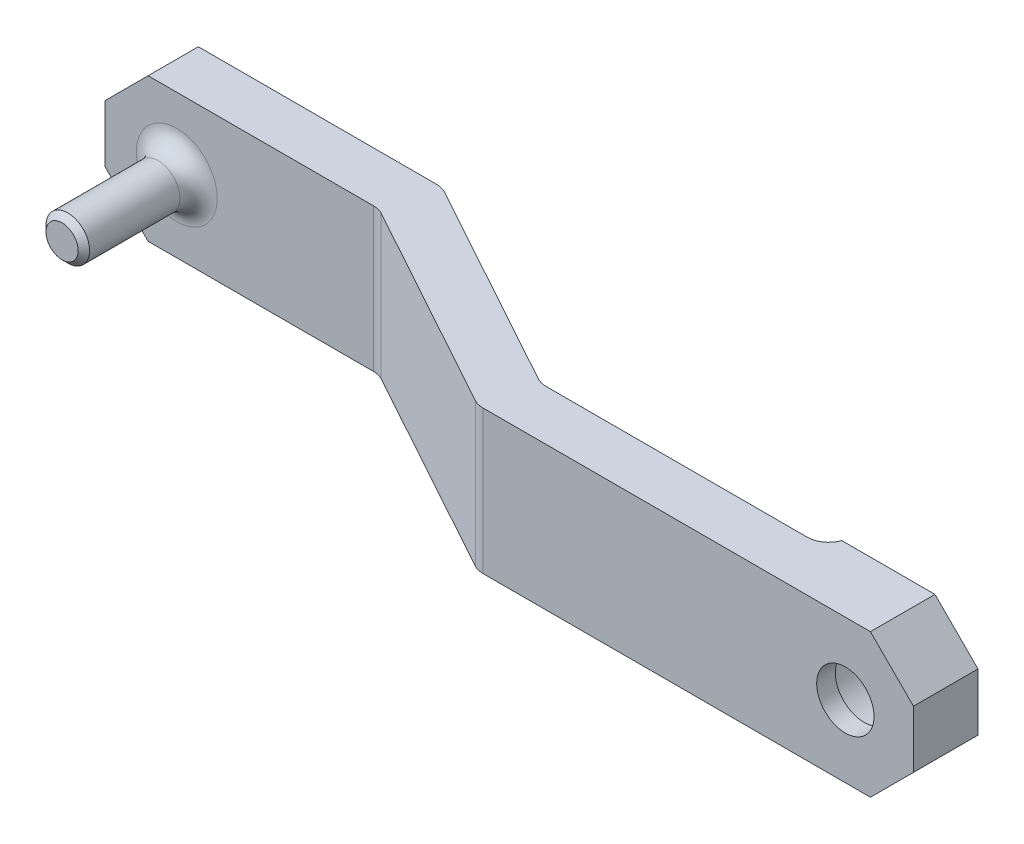
SolidWorks part; units mm, degrees
material "PLA"
ref_plane "Front Plane" through (0, 0, 0) normal (0, 0, 1) x (1, 0, 0)
ref_plane "Top Plane" through (0, 0, 0) normal (0, 1, 0) x (1, 0, 0)
ref_plane "Right Plane" through (0, 0, 0) normal (1, 0, 0) x (0, 0, -1)
sketch "Sketch1" plane through (0, 0, 0) normal (0, 1, 0) x (1, 0, 0)
  line L0 (0, 0) -> (0, -4.445)
  line L1 (0, -4.445) -> (24.2582, -4.445)
  line L2 (24.2582, -4.445) -> (43.6257, -15.0975)
  line L3 (43.6257, -15.0975) -> (82.2325, -15.0975)
  line L4 (82.2325, -15.0975) -> (82.2325, -9.3825)
  line L5 (82.2325, -9.3825) -> (70.1675, -9.3825)
  line L6 (70.1675, -9.3825) -> (70.1675, -10.6525)
  line L7 (70.1675, -10.6525) -> (44.7675, -10.6525)
  line L8 (44.7675, -10.6525) -> (25.4, 0)
  line L9 (25.4, 0) -> (0, 0)
  line L10 (76.2, -9.3825) -> (76.2, -12.3825) construction
  line L11 (6.35, 0) -> (6.35, -4.445) construction
  line L12 (100.0125, -12.3825) -> (76.2, -12.3825) construction
  line L13 (0, -2.2225) -> (6.35, -2.2225) construction
  dimension "D1" = 12.065
  dimension "D2" = 6.35
  dimension "D3" = 69.85
  dimension "D4" = 10.16
  dimension "D5" = 5.715
  dimension "D6" = 4.445
  dimension "D7" = 4.445
  dimension "D8" = 4.445
  dimension "D9" = 25.4
  dimension "D10" = 25.4
  dimension "D11" = 3
extrude "Boss-Extrude1" add sketch "Sketch1" along normal blind 12.7
sketch "Sketch2" plane through (0, 0, 9.3825) normal (0, 0, -1) x (-1, 0, 0)
  line L0 (-76.2, 12.7) -> (-76.2, 0) construction
  line L1 (-82.2325, 12.7) -> (-70.1675, 12.7) construction
  line L2 (-82.2325, 0) -> (-70.1675, 0) construction
  circle A0 centre (-76.2, 6.35) radius 4.1148
  dimension "D1" = 8.2296
extrude "Cut-Extrude1" cut sketch "Sketch2" against normal blind 4.064
sketch "Sketch3" plane through (0, 0, 13.4465) normal (0, 0, -1) x (-1, 0, 0)
  circle A0 centre (-76.2, 6.35) radius 2.54
  dimension "D1" = 5.08
extrude "Cut-Extrude2" cut sketch "Sketch3" against normal through all
sketch "Sketch4" plane through (0, 0, 4.445) normal (0, 0, -1) x (-1, 0, 0)
  line L0 (0, 6.35) -> (-6.35, 6.35) construction
  line L1 (0, 12.7) -> (0, 0) construction
  circle A0 centre (-6.35, 6.35) radius 1.9304
  dimension "D2" = 3.8608
  dimension "D1" = 6.35
extrude "Boss-Extrude2" add sketch "Sketch4" against normal blind 10.16
fillet "Fillet1" radius 1.651 1 edges at (4.4196, 6.35, 4.445)
chamfer "Chamfer1" distance 3.81 angle 45 4 edges at (82.2325, 0, 12.24) (82.2325, 12.7, 12.24) (0, 0, 2.2225) (0, 12.7, 2.2225)
fillet "Fillet2" radius 1.905 5 edges at (43.6257, 6.35, 15.0975) (24.2582, 6.35, 4.445) (25.4, 6.35, 0) (44.7675, 6.35, 10.6525) (70.1675, 6.35, 10.6525)
chamfer "Chamfer2" distance 0.635 angle 45 1 edges at (72.0852, 6.35, 9.3825)
chamfer "Chamfer3" distance 0.508 angle 45 1 edges at (4.4196, 6.35, 14.605)
